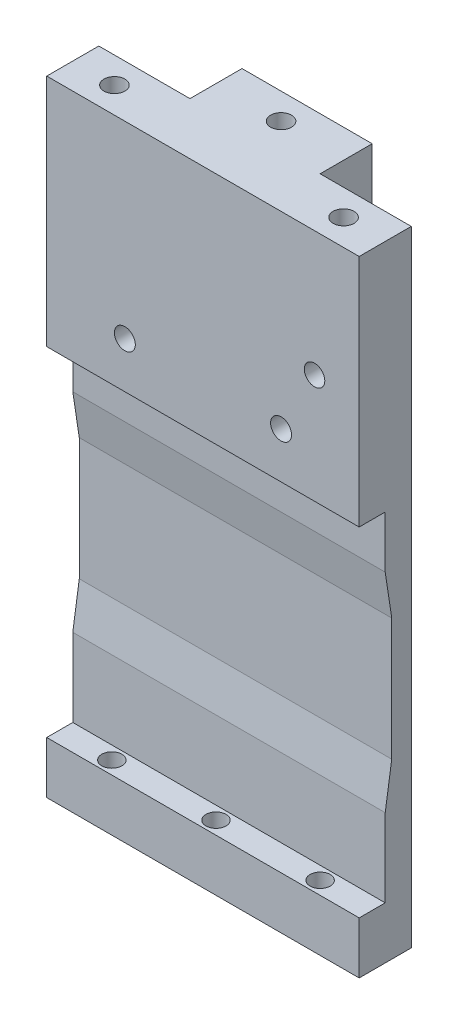
SolidWorks part; units mm, degrees
material "6061 Alloy"
ref_plane "Front Plane" through (0, 0, 0) normal (0, 0, 1) x (1, 0, 0)
ref_plane "Top Plane" through (0, 0, 0) normal (0, 1, 0) x (1, 0, 0)
ref_plane "Right Plane" through (0, 0, 0) normal (1, 0, 0) x (0, 0, -1)
sketch "Sketch1" plane through (0, 0, 0) normal (0, 1, 0) x (1, 0, 0)
  line L0 (-15.875, 6.35) -> (-15.875, 19.05)
  line L1 (38.1, -6.35) -> (-38.1, -6.35)
  line L2 (38.1, -6.35) -> (38.1, 6.35)
  line L3 (38.1, 6.35) -> (15.875, 6.35)
  line L4 (-38.1, -6.35) -> (-38.1, 6.35)
  line L5 (38.1, -6.35) -> (-38.1, 6.35) construction
  line L6 (38.1, 6.35) -> (-38.1, -6.35) construction
  line L7 (-15.875, 19.05) -> (15.875, 19.05)
  line L8 (15.875, 19.05) -> (15.875, 6.35)
  line L9 (-15.875, 6.35) -> (-38.1, 6.35)
  line L10 (0, 19.05) -> (0, 0) construction
  point P0 (0, 0)
  dimension "D1" = 76.2
  dimension "D2" = 12.7
  dimension "D3" = 31.75
  dimension "D4" = 12.7
extrude "Boss-Extrude1" add sketch "Sketch1" along normal mid plane 152.4
ref_plane "Plane1" through (0, 0, 0) normal (0, 1, 0) x (1, 0, 0)
sketch "Sketch5" plane through (0, 0, 0) normal (0, 1, 0) x (1, 0, 0)
  line L0 (-4.7625, 19.05) -> (-4.7625, 12.7)
  line L1 (15.875, 19.05) -> (-15.875, 19.05) construction
  line L2 (4.7625, 12.7) -> (4.7625, 19.05)
  line L3 (0, 0) -> (0, 12.7) construction
  line L4 (-4.7625, 19.05) -> (4.7625, 19.05)
  arc A0 (-4.7625, 12.7) -> (4.7625, 12.7) centre (0, 12.7) ccw
  point P10 (0, 7.9375)
  dimension "D1" = 11.1125
  dimension "D2" = 9.525
extrude "Cut-Extrude3" cut sketch "Sketch5" against normal mid plane 95.25
sketch "Sketch9" plane through (0, 0, 0) normal (1, 0, 0) x (0, 0, -1)
  line L0 (19.05, -52.3875) -> (12.7, -52.3875)
  line L1 (19.05, -52.3875) -> (19.05, -47.625)
  line L2 (19.05, -47.625) -> (7.9375, -47.625) construction
  line L3 (12.7, -52.3875) -> (12.7, -47.625) construction
  line L4 (7.9375, -47.625) -> (19.05, -47.625)
  arc A0 (12.7, -52.3875) -> (7.9375, -47.625) centre (12.7, -47.625) cw
  dimension "D2" = 90
  dimension "D1" = 4.7625
  dimension "D3" = 11.1125
revolve "Cut-Revolve1" cut sketch "Sketch9" angle 360 about L4
mirror "Mirror1" about plane through (0, 0, 0) normal (0, 1, 0) of "Cut-Revolve1"
ref_plane "Parting Plane" through (0, 0, 0) normal (0, 0, 1) x (1, 0, 0)
sketch "Sketch12" plane through (38.1, 0, 0) normal (1, 0, 0) x (0, 0, -1)
  line L0 (-6.35, -63.5) -> (0, -63.5)
  line L1 (-6.35, 76.2) -> (-6.35, -76.2) construction
  line L2 (0, 45.4834) -> (0, -45.4834) construction
  line L3 (0, -63.5) -> (0, -44.45)
  line L4 (0, -44.45) -> (1.5875, -33.9561)
  line L5 (1.5875, -33.9561) -> (1.5875, -4.1439)
  line L6 (1.5875, -4.1439) -> (0, 6.35)
  line L7 (0, 6.35) -> (0, 19.05)
  line L8 (0, 19.05) -> (-6.35, 19.05)
  line L9 (-6.35, 19.05) -> (-6.35, -63.5)
  line L10 (-6.35, -76.2) -> (6.35, -76.2) construction
  dimension "D1" = 19.05
  dimension "D2" = 12.7
  dimension "D3" = 82.55
  dimension "D4" = 1.5875
  dimension "D5" = 12.7
extrude "Cut-Extrude4" cut sketch "Sketch12" against normal through all
hole_wizard "#10 (0.1935) Diameter Hole1" positions "Sketch15" profile "Sketch16" hole size "#10" standard "ANSI Inch"
sketch "Sketch15" plane through (0, -76.2, 0) normal (0, -1, 0) x (-1, 0, 0)
  line L0 (38.1, 6.35) -> (38.1, -6.35) construction
  line L1 (-38.1, -6.35) -> (-38.1, 6.35) construction
  line L3 (25.4, -3.175) -> (-25.4, -3.175) construction
  line L4 (38.1, -6.35) -> (-38.1, -6.35) construction
  point P0 (25.4, -3.175)
  point P2 (-25.4, -3.175)
  point P16 (0, -3.175)
  dimension "D1" = 12.7
  dimension "D2" = 12.7
  dimension "D3" = 3.175
sketch "Sketch16" plane through (-25.4, -76.2, 3.175) normal (1, 0, 0) x (0, 0, -1)
  line L0 (0, 0) -> (0, 20.5266)
  line L1 (0, 20.5266) -> (2.4574, 19.05)
  line L2 (2.4574, 19.05) -> (2.4574, 0)
  line L5 (2.4574, 0) -> (0, 0)
  line L10 (0, 20.5266) -> (-2.4575, 19.05) construction
  line L11 (0, -6.35) -> (0, 107.95) construction
  dimension "Hole Dia." = 4.9149
  dimension "Hole Depth" = 19.05
  dimension "Drill Angle" = 118
hole_wizard "1/4-20 Tapped Hole1" positions "Sketch17" profile "Sketch18" tap size "1/4-20" standard "ANSI Inch" end condition through all
sketch "Sketch17" plane through (0, 76.2, 0) normal (0, 1, 0) x (1, 0, 0)
  line L0 (15.875, 19.05) -> (-15.875, 19.05) construction
  line L1 (15.875, 6.35) -> (15.875, 19.05) construction
  point P0 (0, 12.7)
  dimension "D1" = 6.35
  dimension "D2" = 15.875
sketch "Sketch18" plane through (0, 76.2, -12.7) normal (1, 0, 0) x (0, 0, 1)
  line L0 (0, 0) -> (0, 152.4)
  line L1 (0, 152.4) -> (2.5527, 152.4)
  line L2 (2.5527, 152.4) -> (2.5527, 0)
  line L5 (2.5527, 0) -> (0, 0)
  line L11 (0, -6.35) -> (0, 107.95) construction
  dimension "Thru Tap Drill Dia." = 5.1054
  dimension "Thru Tap Drill Depth" = 152.4
cosmetic thread "Hole Thread1" parameters "D2"=6.35
sketch "Sketch19" plane through (0, 0, -6.35) normal (0, 0, -1) x (-1, 0, 0)
  line L0 (-38.1, 76.2) -> (-15.875, 76.2) construction
  circle A0 centre (-27.209, 45.72) radius 2.5
  dimension "D1" = 5
  dimension "D2" = 30.48
extrude "Cut-Extrude5" cut sketch "Sketch19" against normal through all
hole_wizard "1/4-20 Tapped Hole2" positions "Sketch20" profile "Sketch21" tap size "1/4-20" standard "ANSI Inch"
sketch "Sketch20" plane through (0, 76.2, 0) normal (0, 1, 0) x (1, 0, 0)
  point P0 (27.94, 0)
  point P3 (-27.94, 0)
sketch "Sketch21" plane through (27.94, 76.2, 0) normal (1, 0, 0) x (0, 0, 1)
  line L0 (0, 0) -> (0, 22.225)
  line L1 (0, 22.225) -> (2.5527, 20.6912)
  line L2 (2.5527, 20.6912) -> (2.5527, 0)
  line L5 (2.5527, 0) -> (0, 0)
  line L10 (0, 22.225) -> (-2.5527, 20.6912) construction
  line L11 (0, -6.35) -> (0, 107.95) construction
  dimension "Tap Drill Dia." = 5.1054
  dimension "Tap Drill Depth" = 22.225
  dimension "Drill Angle" = 118
cosmetic thread "Hole Thread2" parameters "D1"=38.26, "D2"=6.35
cosmetic thread "Hole Thread3" parameters "D1"=38.26, "D2"=6.35
hole_wizard "1/4-20 Tapped Hole3" positions "Sketch22" profile "Sketch23" tap size "1/4-20" standard "ANSI Inch"
sketch "Sketch22" plane through (0, 0, -19.05) normal (0, 0, -1) x (-1, 0, 0)
  line L0 (9.525, 57.15) -> (-9.525, 57.15) construction
  line L2 (0, 57.15) -> (0, 0) construction
  line L4 (-15.875, -76.2) -> (15.875, -76.2) construction
  line L5 (-9.525, 57.15) -> (-9.525, -66.675) construction
  line L7 (-9.525, -66.675) -> (9.525, -66.675) construction
  point P0 (-9.525, -66.675)
  point P2 (9.525, 57.15)
  point P4 (-9.525, 57.15)
  point P26 (9.525, -66.675)
  dimension "D1" = 19.05
  dimension "D2" = 123.825
  dimension "D3" = 9.525
  dimension "D4" = 19.05
sketch "Sketch23" plane through (9.525, -66.675, -19.05) normal (1, 0, 0) x (0, 1, 0)
  line L0 (0, 0) -> (0, 10.5838)
  line L1 (0, 10.5838) -> (2.5527, 9.05)
  line L2 (2.5527, 9.05) -> (2.5527, 0)
  line L5 (2.5527, 0) -> (0, 0)
  line L10 (0, 10.5838) -> (-2.5527, 9.05) construction
  line L11 (0, -6.35) -> (0, 107.95) construction
  dimension "Tap Drill Dia." = 5.1054
  dimension "Tap Drill Depth" = 9.05
  dimension "Drill Angle" = 118
cosmetic thread "Hole Thread4" parameters "D1"=38.26, "D2"=6.35
cosmetic thread "Hole Thread5" parameters "D1"=38.26, "D2"=6.35
cosmetic thread "Hole Thread6" parameters "D1"=38.26, "D2"=6.35
cosmetic thread "Hole Thread9" parameters "D1"=38.26, "D2"=6.35
hole_wizard "1/4-20 Tapped Hole4" positions "Sketch24" profile "Sketch25" tap size "1/4-20" standard "ANSI Inch"
sketch "Sketch24" plane through (0, 0, 6.35) normal (0, 0, 1) x (1, 0, 0)
  point P0 (19.05, 30.2607)
  point P3 (-19.05, 30.2607)
sketch "Sketch25" plane through (19.05, 30.2607, 6.35) normal (1, 0, 0) x (0, -1, 0)
  line L0 (0, 0) -> (0, 8.89)
  line L1 (0, 8.89) -> (2.5527, 7.3562)
  line L2 (2.5527, 7.3562) -> (2.5527, 0)
  line L5 (2.5527, 0) -> (0, 0)
  line L10 (0, 8.89) -> (-2.5527, 7.3562) construction
  line L11 (0, -6.35) -> (0, 107.95) construction
  dimension "Tap Drill Dia." = 5.1054
  dimension "Tap Drill Depth" = 8.89
  dimension "Drill Angle" = 118
cosmetic thread "Hole Thread7" parameters "D1"=12.7, "D2"=6.35
cosmetic thread "Hole Thread8" parameters "D1"=12.7, "D2"=6.35
